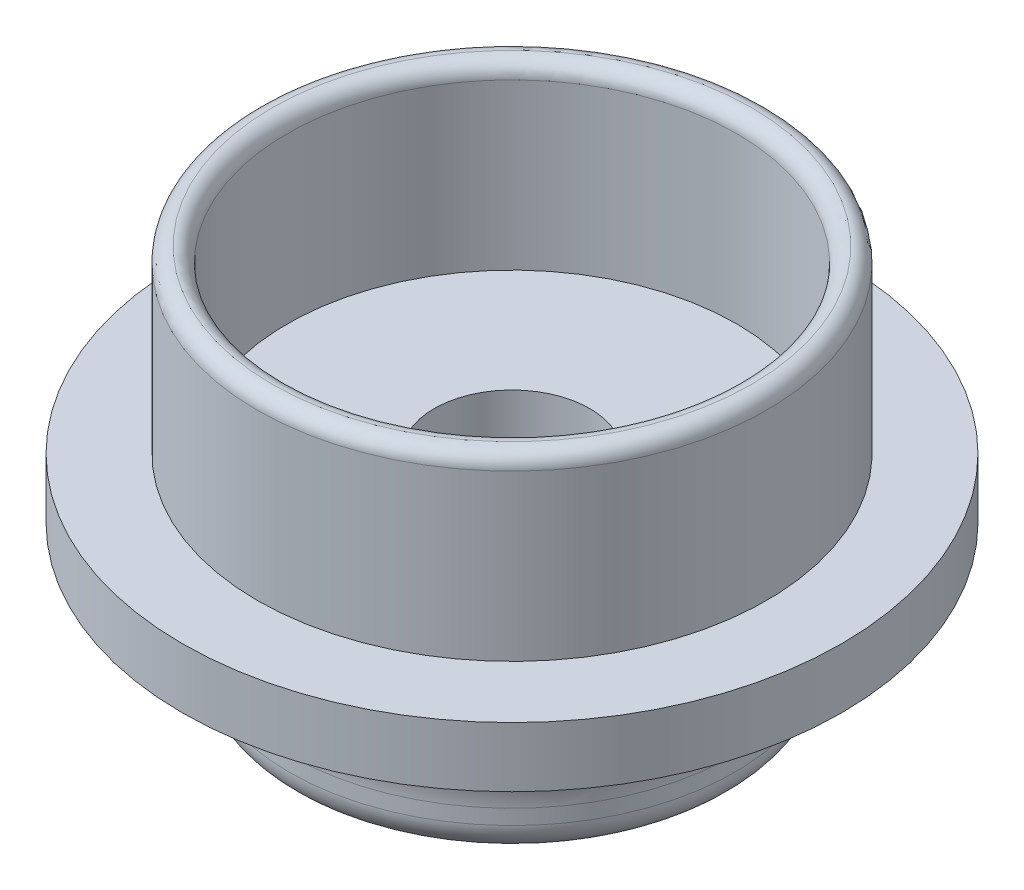
SolidWorks part; units mm, degrees
ref_plane "Front Plane" through (0, 0, 0) normal (0, 0, 1) x (1, 0, 0)
ref_plane "Top Plane" through (0, 0, 0) normal (0, 1, 0) x (1, 0, 0)
ref_plane "Right Plane" through (0, 0, 0) normal (1, 0, 0) x (0, 0, -1)
sketch "Sketch1" plane through (0, 0, 0) normal (0, 1, 0) x (1, 0, 0)
  circle A0 centre (0, 0) radius 11
  dimension "D1" = 22
extrude "Boss-Extrude1" add sketch "Sketch1" along normal blind 2
sketch "Sketch2" plane through (0, 2, 0) normal (0, 1, 0) x (1, 0, 0)
  circle A0 centre (0, 0) radius 8.5
  circle A1 centre (0, 0) radius 7.5
  dimension "D1" = 17
  dimension "D2" = 15
extrude "Boss-Extrude2" add sketch "Sketch2" along normal blind 6
sketch "Sketch3" plane through (0, 2, 0) normal (0, 1, 0) x (1, 0, 0)
  circle A0 centre (0, 0) radius 2.6
  dimension "D1" = 5.2
extrude "Cut-Extrude1" cut sketch "Sketch3" against normal through all
sketch "Sketch4" plane through (0, 0, 0) normal (0, -1, 0) x (1, 0, 0)
  line L0 (4.6, -2.6558) -> (4.6, 2.6558)
  line L1 (4.6, 2.6558) -> (0, 5.3116)
  line L2 (0, 5.3116) -> (-4.6, 2.6558)
  line L3 (-4.6, 2.6558) -> (-4.6, -2.6558)
  line L4 (-4.6, -2.6558) -> (0, -5.3116)
  line L5 (0, -5.3116) -> (4.6, -2.6558)
  circle A0 centre (0, 0) radius 4.6
  circle A1 centre (0, 0) radius 7.4336
  dimension "D1" = 9.2
extrude "Boss-Extrude3" add sketch "Sketch4" along normal blind 4.5 contours A1 L5 L4 L3 L2 L1 L0 region at (-7.2234, 0, 0)
fillet "Fillet1" radius 3 1 edges at (0, 0, -7.4336)
fillet "Fillet2" radius 1 1 edges at (0, -4.5, -7.4336)
fillet "Fillet3" radius 0.5 2 edges at (0, 8, 8.5) (0, 8, 7.5)
